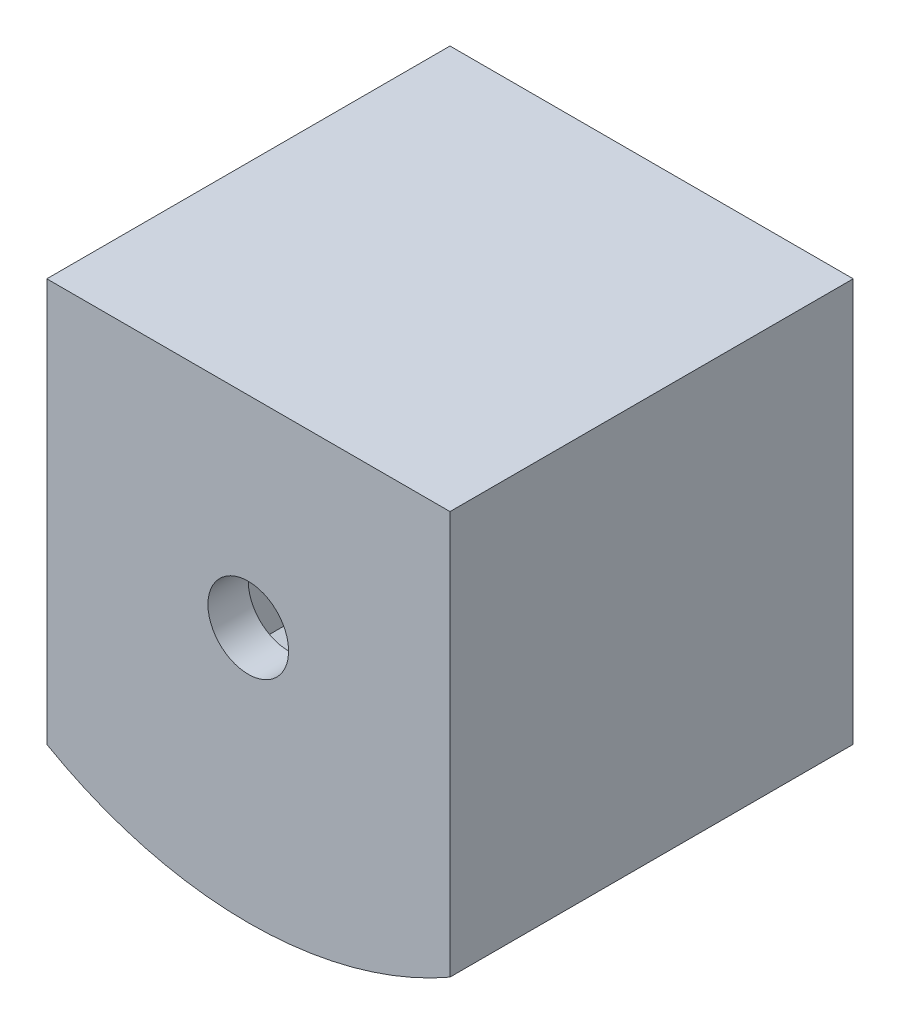
SolidWorks part; units mm, degrees
ref_plane "Front Plane" through (0, 0, 0) normal (0, 0, 1) x (1, 0, 0)
ref_plane "Top Plane" through (0, 0, 0) normal (0, 1, 0) x (1, 0, 0)
ref_plane "Right Plane" through (0, 0, 0) normal (1, 0, 0) x (0, 0, -1)
sketch "Sketch1" plane through (0, 0, 0) normal (0, 0, 1) x (1, 0, 0)
  line L2 (15, -15) -> (15, 15)
  line L3 (15, 15) -> (-15, 15)
  line L4 (-15, -15) -> (-15, 15)
  line L5 (15, -15) -> (-15, 15) construction
  line L6 (15, 15) -> (-15, -15) construction
  arc A3 (-15, -15) -> (15, -15) centre (0, 11.0962) ccw
  point P0 (0, 0)
extrude "Boss-Extrude1" add sketch "Sketch1" along normal blind 30
shell "Shell13" thickness 3 removed face at (0, -1.001, 0)
sketch "Sketch3" plane through (0, 0, 27) normal (0, 0, -1) x (-1, 0, 0)
  circle A0 centre (0.0103, 0.0076) radius 3
  point P2 (0.0103, 0.0076)
  point P3 (0, 0)
extrude "Cut-Extrude2" cut sketch "Sketch3" against normal blind 3
sketch "Sketch4" plane through (0, 0, 0) normal (0, 0, -1) x (-1, 0, 0)
  line L0 (12, 12) -> (12, -13.2022) construction
  line L1 (-5, 14) -> (5, 14)
  line L2 (-5, 14) -> (-5, 13)
  line L3 (-5, 13) -> (5, 13)
  line L4 (5, 14) -> (5, 13)
  line L5 (-14, 5) -> (-13, 5)
  line L6 (-14, 5) -> (-14, -5)
  line L7 (-14, -5) -> (-13, -5)
  line L8 (-13, 5) -> (-13, -5)
  line L9 (-3.5, -17) -> (3.5, -17)
  line L10 (-3.5, -17) -> (-3.5, -18)
  line L11 (-3.5, -18) -> (3.5, -18)
  line L12 (3.5, -17) -> (3.5, -18)
  line L13 (13, 5) -> (14, 5)
  line L14 (13, 5) -> (13, -5)
  line L15 (13, -5) -> (14, -5)
  line L16 (14, 5) -> (14, -5)
  line L17 (-12, -13.2022) -> (-12, 12) construction
  line L18 (-12, 12) -> (12, 12) construction
  point P16 (0, -17)
  point P18 (-13, 0)
  point P19 (13, 0)
  point P20 (0, 13)
  dimension "D1" = 1
  dimension "D2" = 1
  dimension "D3" = 1
  dimension "D4" = 17
extrude "Cut-Extrude3" cut sketch "Sketch4" against normal blind 5
